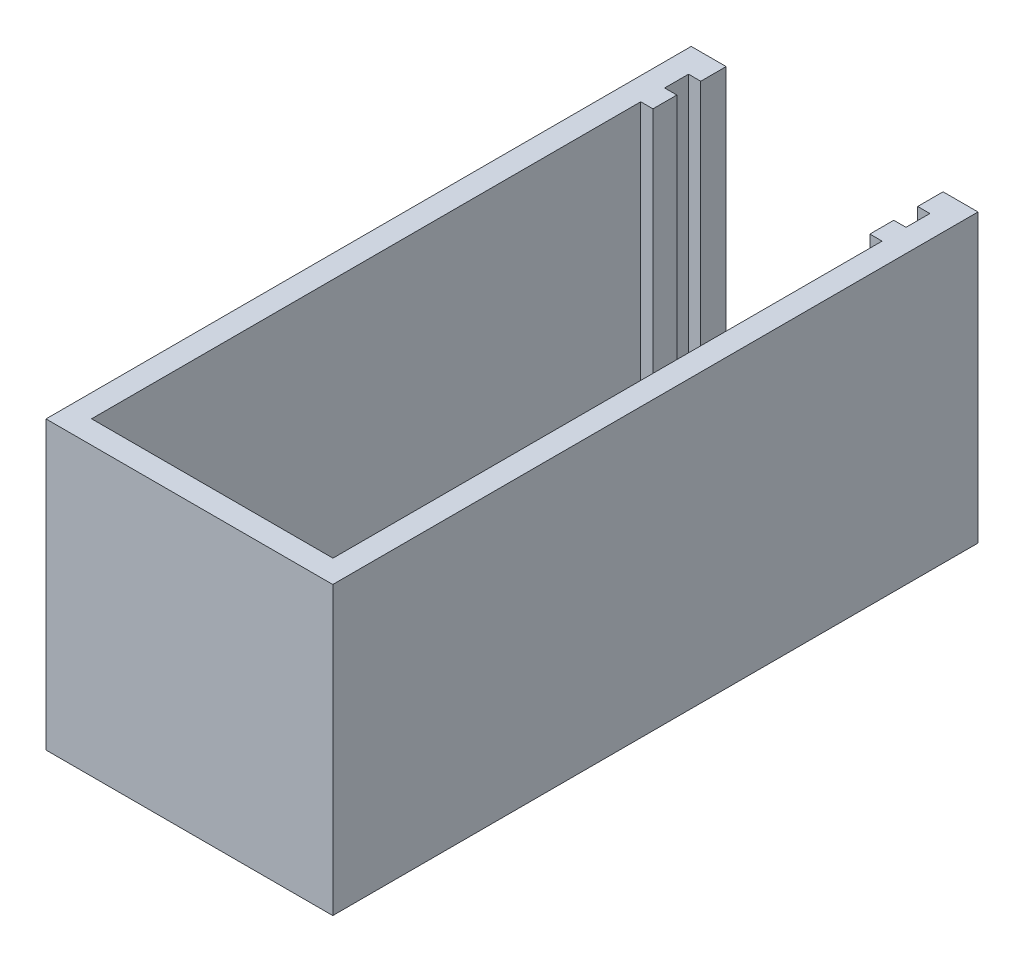
SolidWorks part; units mm, degrees
ref_plane "Front Plane" through (0, 0, 0) normal (0, 0, 1) x (1, 0, 0)
ref_plane "Top Plane" through (0, 0, 0) normal (0, 1, 0) x (1, 0, 0)
ref_plane "Right Plane" through (0, 0, 0) normal (1, 0, 0) x (0, 0, -1)
sketch "Sketch1" plane through (0, 0, 0) normal (0, 1, 0) x (1, 0, 0)
  line L0 (0, 0) -> (-6, 0)
  line L1 (0, 0) -> (6, 0)
  line L2 (6, 0) -> (6, -27)
  line L3 (6, -27) -> (-6, -27)
  line L4 (-6, -27) -> (-6, 0)
extrude "Boss-Extrude1" add sketch "Sketch1" along normal blind 12
sketch "Sketch2" plane through (0, 12, 0) normal (0, 1, 0) x (1, 0, 0)
  line L0 (0, 0) -> (0, -1.0632)
  line L1 (0, 0) -> (0, -27) construction
  line L2 (-5.05, -1.0632) -> (5.05, -1.0632)
  line L3 (-6, -27) -> (6, -27) construction
  line L4 (-5.05, -3.0632) -> (-5.05, -26.0423)
  line L5 (5.05, -1.0632) -> (5.05, -2.0632)
  line L6 (5.05, -2.0632) -> (4.5384, -2.0632)
  line L7 (4.5384, -2.0632) -> (4.5384, -3.0632)
  line L8 (4.5384, -3.0632) -> (5.05, -3.0632)
  line L9 (5.05, -3.0632) -> (5.05, -26.0423)
  line L10 (5.05, -26.0423) -> (-5.05, -26.0423)
  line L11 (-4.5384, -3.0632) -> (-5.05, -3.0632)
  line L12 (-4.5384, -2.0632) -> (-4.5384, -3.0632)
  line L13 (-5.05, -2.0632) -> (-4.5384, -2.0632)
  line L14 (-5.05, -1.0632) -> (-5.05, -2.0632)
  point P14 (0, -26.0423)
extrude "Cut-Extrude1" cut sketch "Sketch2" against normal blind 11 and the other way through all contours L10 L4 L11 L12 L13 L14 L2 L5 L6 L7 L8 L9
sketch "Sketch3" plane through (0, 0, 0) normal (0, 0, -1) x (-1, 0, 0)
  line L0 (4.5384, 12) -> (4.5384, 1) construction
  line L1 (4.5384, 12) -> (4.5384, 1)
  line L2 (-4.5384, 12) -> (-4.5384, 1) construction
  line L3 (-4.5384, 12) -> (-4.5384, 1)
  line L4 (-4.5384, 1) -> (4.5384, 1)
  line L5 (-4.5384, 12) -> (4.5384, 12)
extrude "Cut-Extrude2" cut sketch "Sketch3" against normal blind 11 contours L5 L1 L4 L3
